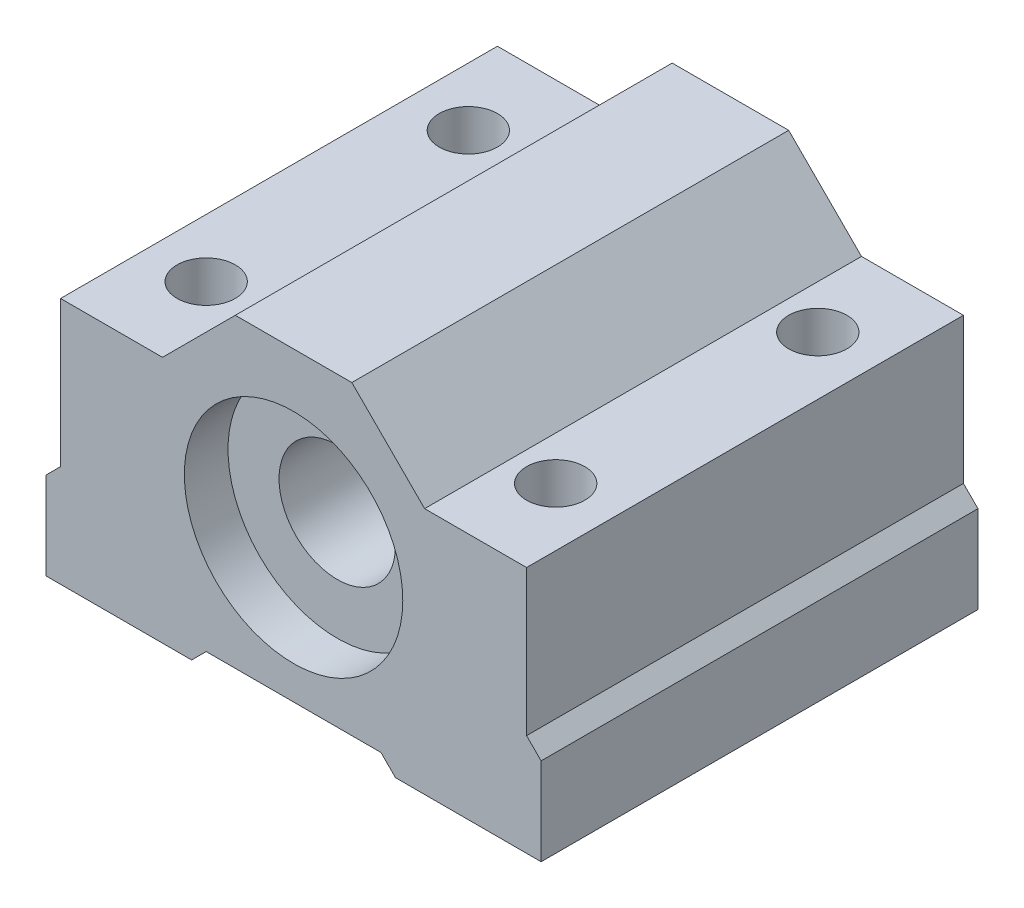
SolidWorks part; units mm, degrees
material "6061 Alloy"
ref_plane "Front Plane" through (0, 0, 0) normal (0, 0, 1) x (1, 0, 0)
ref_plane "Top Plane" through (0, 0, 0) normal (0, 1, 0) x (1, 0, 0)
ref_plane "Right Plane" through (0, 0, 0) normal (1, 0, 0) x (0, 0, -1)
sketch "Sketch1" plane through (0, 0, 0) normal (0, 0, 1) x (1, 0, 0)
  line L0 (17, -10.7864) -> (17, -4.7864)
  line L1 (-17, -10.7864) -> (-7, -10.7864)
  line L2 (-17, -10.7864) -> (-17, -4.7864)
  line L3 (-4, 11.2136) -> (4, 11.2136)
  line L4 (17, -10.7864) -> (17, -4.7864)
  line L5 (-17, -10.7864) -> (17.6578, 11.2038) construction
  line L6 (-17.0966, 10.8477) -> (17, -10.7864) construction
  line L7 (0, -55) -> (0, 55) construction
  line L8 (16, -3.7864) -> (16, 6.2136)
  line L9 (16, 6.2136) -> (9, 6.2136)
  line L10 (9, 6.2136) -> (4, 11.2136)
  line L11 (17, -4.7864) -> (16, -3.7864)
  line L12 (-17, -10.7864) -> (-17, -4.7864)
  line L13 (-17, -4.7864) -> (-16, -3.7864)
  line L14 (-16, -3.7864) -> (-16, 6.2136)
  line L15 (-16, 6.2136) -> (-9, 6.2136)
  line L16 (-9, 6.2136) -> (-4, 11.2136)
  line L18 (-6, -9.7864) -> (6, -9.7864)
  line L20 (6, -9.7864) -> (7, -10.7864)
  line L21 (-6, -9.7864) -> (-7, -10.7864)
  line L22 (7, -10.7864) -> (17, -10.7864)
  point P0 (0, 0)
  point P22 (0, -9.7864)
  dimension "D1" = 22
  dimension "D2" = 34
  dimension "D3" = 6
  dimension "D4" = 1
  dimension "D5" = 45
  dimension "D6" = 7
  dimension "D7" = 135
  dimension "D8" = 10
  dimension "D9" = 12
  dimension "D11" = 45
  dimension "D12" = 45
extrude "Boss-Extrude1" add sketch "Sketch1" along normal blind 15 and the other way blind 15 contours L16 L15 L14 L13 L2 L1 L0 L11 L8 L9 L10 L3 region at (0, -1.0874, 0)
sketch "Sketch2" plane through (0, 0, 0) normal (0, 0, 1) x (1, 0, 0)
  circle A0 centre (0, 0) radius 7.5
  dimension "D1" = 15
extrude "Cut-Extrude1" cut sketch "Sketch2" against normal through all from offset 12 offset against normal yes
mirror "Mirror1" about plane through (0, 0, 0) normal (0, 0, 1) of "Cut-Extrude1"
sketch "Sketch3" plane through (0, 0, 12) normal (0, 0, 1) x (1, 0, 0)
  circle A0 centre (0, 0) radius 4
  dimension "D1" = 8
extrude "Cut-Extrude2" cut sketch "Sketch3" against normal through all
sketch "Sketch4" plane through (0, -10.7864, 0) normal (0, -1, 0) x (1, 0, 0)
  line L0 (7, 15) -> (17, 15) construction
  line L1 (17, -15) -> (17, 15) construction
  line L2 (0, -12.1) -> (0, 12.1) construction
  line L3 (12.1, 0) -> (-12.1, 0) construction
  circle A0 centre (12, 9) radius 2
  circle A1 centre (-12, 9) radius 2
  circle A2 centre (12, -9) radius 2
  circle A3 centre (-12, -9) radius 2
  dimension "D3" = 4
  dimension "D1" = 6
  dimension "D2" = 5
extrude "Cut-Extrude3" cut sketch "Sketch4" against normal through all
